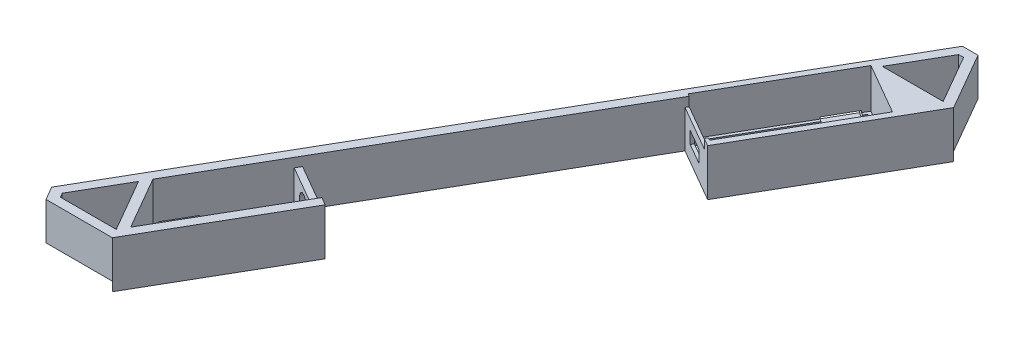
SolidWorks part; units mm, degrees
ref_plane "Front Plane" through (0, 0, 0) normal (0, 0, 1) x (1, 0, 0)
ref_plane "Top Plane" through (0, 0, 0) normal (0, 1, 0) x (1, 0, 0)
ref_plane "Right Plane" through (0, 0, 0) normal (1, 0, 0) x (0, 0, -1)
sketch "Sketch1" plane through (0, 0, 0) normal (0, 1, 0) x (1, 0, 0)
  line L24 (-11.7321, 167.8653) -> (3.2679, 159.2051)
  line L29 (3.2679, 159.2051) -> (-18.2321, 121.966) construction
  line L31 (-107.8246, -1.4282) -> (-108.6491, 0)
  line L40 (-0.8246, 186.7576) -> (0.8246, 186.7576)
  line L41 (-109.5566, -4.4282) -> (-112.1132, 0)
  line L42 (-2.5566, 189.7576) -> (-112.1132, 0)
  line L44 (-2.5566, 189.7576) -> (2.5566, 189.7576)
  line L50 (-99.4737, 15.8923) -> (-89.4737, -1.4282)
  line L51 (-107.8246, -1.4282) -> (-89.4737, -1.4282)
  line L52 (-99.4737, 15.8923) -> (-108.6491, 0)
  line L62 (-10, 170.8653) -> (10, 170.8653)
  line L63 (-10, 170.8653) -> (-0.8246, 186.7576)
  line L64 (0.8246, 186.7576) -> (10, 170.8653)
  line L65 (2.5566, 189.7576) -> (13.4641, 170.8653)
  line L71 (-109.5566, -4.4282) -> (-87.7417, -4.4282)
  line L82 (-39.7369, 84.7186) -> (-37.1388, 83.2186)
  line L96 (13.4641, 170.8653) -> (-16.134, 119.6)
  line L100 (-18.2321, 121.966) -> (-33.2321, 130.6262)
  line L102 (-11.7321, 167.8653) -> (-33.2321, 130.6262)
  line L104 (-33.7321, 129.7602) -> (-97.7417, 18.8923)
  line L111 (-33.7321, 129.7602) -> (-18.7321, 121.1)
  line L113 (-16.134, 119.6) -> (-18.7321, 121.1)
  line L115 (-18.7321, 121.1) -> (-18.2321, 121.966)
  line L117 (-18.2321, 121.966) -> (3.2679, 159.2051)
  line L119 (-33.7321, 129.7602) -> (-33.2321, 130.6262)
  line L121 (-97.7417, 18.8923) -> (-80.7417, 48.3372) construction
  line L123 (-80.7417, 48.3372) -> (-65.7417, 39.6769)
  line L127 (-82.7417, 10.2321) -> (-65.7417, 39.6769)
  line L133 (-65.7417, 39.6769) -> (-64.7417, 41.409)
  line L134 (-64.7417, 41.409) -> (-79.7417, 50.0692)
  line L135 (-64.7417, 41.409) -> (-62.1436, 39.909)
  line L137 (-87.7417, -4.4282) -> (-62.1436, 39.909)
  line L138 (-97.7417, 18.8923) -> (-87.7417, 1.5718)
  line L141 (-82.7417, 10.2321) -> (-87.7417, 1.5718)
  dimension "D1" = 43
  dimension "D2" = 34
  dimension "D3" = 2
extrude "Boss-Extrude2" add sketch "Sketch1" along normal blind 15.38 contours L41 L71 L65 L44 L42 L40 L64 L62 L63 L52 L50 L51 L31 region at (-24.4848, 0, -150.4021)
extrude "Boss-Extrude3" add sketch "Sketch1<11>" along normal blind 1 contours L24 L102 L100 | L127 L123 L104 region at (-14.9821, 0, -144.9157) region at (-82.7246, 0, -26.842)
sketch "Sketch1<11>" plane through (0, 0, 0) normal (0, 1, 0) x (1, 0, 0) same geometry as "Sketch1"
extrude "Boss-Extrude4" add sketch "Sketch1<12>" along normal blind 12.38 contours L119 L111 L115 L100 | L133 L134 L104 L123 region at (-25.9821, 0, -125.8631) region at (-72.7417, 0, -44.8731)
sketch "Sketch1<12>" plane through (0, 0, 0) normal (0, 1, 0) x (1, 0, 0) same geometry as "Sketch1"
sketch "Sketch10" plane through (47.7548, 0, -82.7138) normal (-0.5, 0, 0.866) x (0.866, 0, 0.5)
  line L0 (-94.0929, 0) -> (-85.4329, 0) construction
  line L1 (-73.7724, 0) -> (-94.0929, 0) construction
  line L2 (-85.4329, 0) -> (-85.4329, 5) construction
  line L3 (-85.4329, 5) -> (-81.4329, 5)
  line L4 (-85.4329, 5) -> (-89.4329, 5)
  line L5 (-81.4329, 5) -> (-81.4329, 9)
  line L6 (-89.4329, 5) -> (-89.4329, 9)
  line L7 (-89.4329, 9) -> (-81.4329, 9)
extrude "Cut-Extrude1" cut sketch "Sketch10" against normal blind 8.26
sketch "Sketch12" plane through (1.7452, 0, -3.0228) normal (0.5, 0, -0.866) x (-0.866, 0, -0.5)
  line L0 (94.0929, 0) -> (85.4329, 0) construction
  line L1 (94.0929, 0) -> (73.7724, 0) construction
  line L2 (85.4329, 0) -> (85.4329, 2.5) construction
  line L3 (85.4329, 2.5) -> (85.4329, 6.5) construction
  circle A0 centre (85.4329, 6.5) radius 4
extrude "Cut-Extrude2" cut sketch "Sketch12" against normal blind 8.26
sketch "Sketch15" plane through (0, 0, 0) normal (0, -1, 0) x (1, 0, 0)
  line L0 (-87.7417, 4.4282) -> (-109.5566, 4.4282)
  line L1 (-109.5566, 4.4282) -> (-112.1132, 0)
  line L2 (-112.1132, 0) -> (-101.2058, -18.8923)
  line L3 (-87.7417, 4.4282) -> (-101.2058, -18.8923)
  line L4 (13.4641, -170.8653) -> (2.5566, -189.7576)
  line L5 (2.5566, -189.7576) -> (-2.5566, -189.7576)
  line L6 (-13.4641, -170.8653) -> (-2.5566, -189.7576)
  line L7 (13.4641, -170.8653) -> (-13.4641, -170.8653)
extrude "Cut-Extrude3" cut sketch "Sketch15" against normal blind 3
sketch "Sketch16" plane through (-84.0849, 0, -48.5465) normal (-0.866, 0, -0.5) x (-0.5, 0, 0.866)
  line L0 (-163.0566, 3) -> (-138.2426, 3) construction
  line L1 (56.0566, 3) -> (31.2426, 3) construction
  line L2 (-138.2426, 3) -> (-128.2426, 3)
  line L3 (-138.2426, 3) -> (-138.2426, 1)
  line L4 (-138.2426, 1) -> (-128.2426, 1)
  line L5 (-128.2426, 3) -> (-128.2426, 1)
  line L6 (31.2426, 3) -> (31.2426, 1)
  line L11 (31.2426, 1) -> (21.2426, 1)
  line L12 (21.2426, 1) -> (21.2426, 3)
  line L13 (21.2426, 3) -> (31.2426, 3)
extrude "Cut-Extrude4" cut sketch "Sketch16" against normal blind 3
sketch "Sketch17" plane through (0, 15.38, 0) normal (0, 1, 0) x (1, 0, 0)
  line L0 (-18.2321, 121.966) -> (-17.366, 121.466)
  line L1 (4.634, 159.5711) -> (-17.366, 121.466)
  line L3 (-33.2321, 130.6262) -> (-34.0981, 131.1262)
  line L4 (-33.2321, 130.6262) -> (-18.2321, 121.966)
  line L5 (-12.0981, 169.2314) -> (4.634, 159.5711)
  line L7 (-34.0981, 131.1262) -> (-12.0981, 169.2314)
extrude "Cut-Extrude5" cut sketch "Sketch17" against normal blind 13
